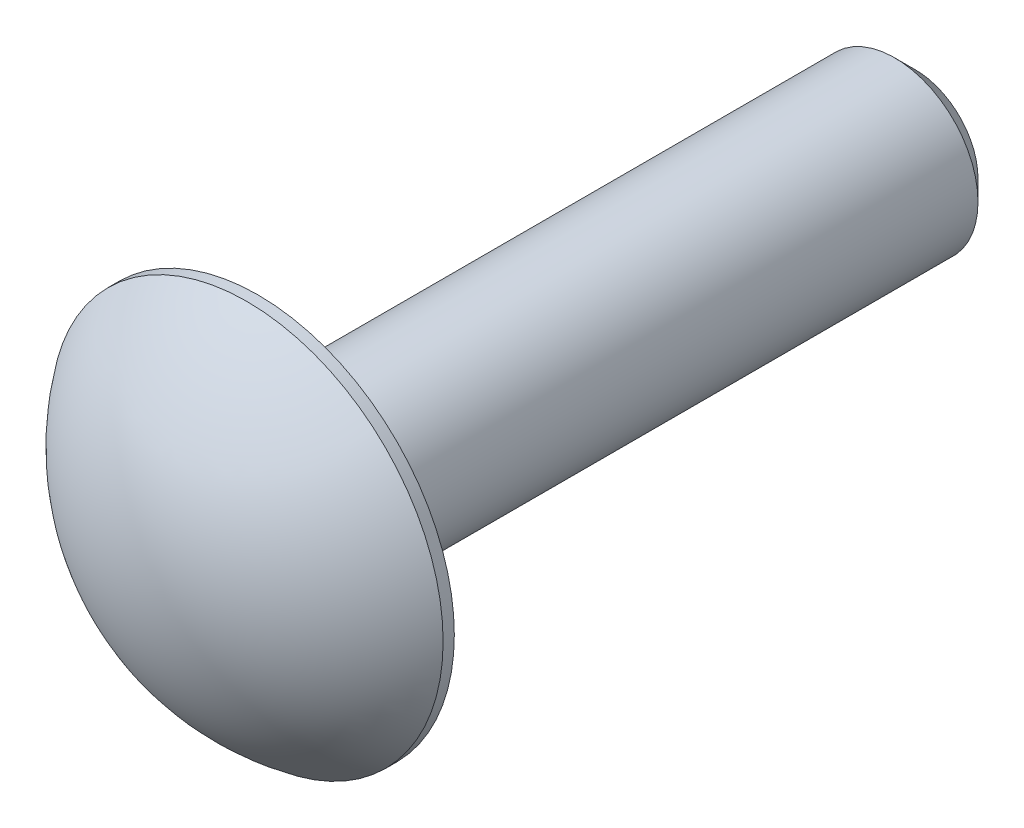
SolidWorks part; units mm, degrees
material "AISI 304"
ref_plane "Front" through (0, 0, 0) normal (0, 0, 1) x (1, 0, 0)
ref_plane "Top" through (0, 0, 0) normal (0, 1, 0) x (1, 0, 0)
ref_plane "Right" through (0, 0, 0) normal (1, 0, 0) x (0, 0, -1)
sketch "Sketch1" plane through (0, 0, 0) normal (0, 0, 1) x (1, 0, 0)
  circle A0 centre (0, 0) radius 5.6896
  dimension "Head Dia" = 11.3792
extrude "Extrude3" add sketch "Sketch1" along normal blind 3.2512
sketch "Sketch11" plane through (0, 0, 0) normal (1, 0, 0) x (0, 0, -1)
  line L0 (0, 0) -> (-3.5052, 0) construction
  line L4 (-3.2512, 5.6896) -> (-3.2512, -5.6896) construction
  line L5 (-3.5052, 6.8275) -> (0, 6.8275)
  line L7 (0, 6.8275) -> (0, 5.6896)
  line L8 (-0.3251, 5.6896) -> (0, 5.6896)
  line L9 (0, -5.6896) -> (0, 5.6896) construction
  line L11 (0, 5.6896) -> (-3.2512, 5.6896) construction
  line L13 (-3.2512, 0) -> (-3.5052, 0)
  line L14 (-3.5052, 0) -> (-3.5052, 6.8275)
  arc A0 (-0.3251, 5.6896) -> (-3.2512, 0) centre (3.7434, 0) ccw
  dimension "D3" = 0.254
  dimension "D1" = 0.3251
  dimension "D5" = 1.1379
revolve "Cut-Revolve3" cut sketch "Sketch11" angle 360 about L0
sketch "Sketch4" plane through (0, 0, 0) normal (1, 0, 0) x (0, 0, -1)
  line L0 (0, 0) -> (19.05, 0)
  line L3 (19.05, 0) -> (19.05, 2.413)
  line L4 (19.05, 2.413) -> (0, 2.413)
  line L6 (0, 2.413) -> (0, 0)
  line L9 (19.05, 2.413) -> (19.05, -2.413) construction
  dimension "length" = 19.05
  dimension "dia" = 4.826
revolve "Revolve1" add sketch "Sketch4" angle 360 about L0
sketch "Sketch13" plane through (0, 0, -19.05) normal (0, 0, -1) x (-1, 0, 0)
  circle A2 centre (0, 0) radius 2.413
curve "Helix/Spiral1" pitch 0.7937 height 22.3012 turns 28.096
chamfer "Chamfer2" distance 0.5953 angle 45 1 edges at (2.413, 0, -19.05)
sketch "Sketch14" plane through (0, 0, 0) normal (1, 0, 0) x (0, 0, -1)
  line L0 (19.05, 2.4378) -> (19.7445, 2.4378)
  line L1 (19.7445, 2.4378) -> (19.4469, 1.9008)
  line L2 (19.4469, 1.9008) -> (19.3477, 1.9008)
  line L3 (19.3477, 1.9008) -> (19.05, 2.4378)
  line L4 (19.1988, 2.1693) -> (19.5957, 2.1693) construction
  dimension "D1" = 0.0992
  dimension "D2" = 58
  dimension "D3" = 0.3969
  dimension "D4" = 0.0248
sweep "Cut-Sweep1" [suppressed] cut profiles "Sketch14" path "Helix/Spiral1"
ref_plane "Plane1" through (0, 0, 19.05) normal (0, 0, -1) x (-1, 0, 0)
sketch "Sketch29" [suppressed] plane through (0, 0, 28.575) normal (0, 0, -1) x (-1, 0, 0)
  circle A0 centre (0, 0) radius 1.7526 construction
  circle A1 centre (0, 0) radius 1.7526
  point P3 (0, -1.7526)
  point P4 (0, 1.7526)
extrude "Extrude11" [suppressed] add sketch "Sketch29" against normal up to surface (28.575 mm away) up to plane "Front"
ref_plane "Plane2" through (0, 0, 3.2512) normal (0, 0, 1) x (1, 0, 0)
sketch "Sketch26" plane through (0, 0, 0) normal (0, 0, 1) x (1, 0, 0)
  circle A1 centre (0, 0) radius 0.5461
  dimension "D1" = 1.0922
extrude "Extrude13" add sketch "Sketch26" along normal up to surface (3.2298 mm away)
sketch "Sketch31" plane through (0, 0, 3.2512) normal (0, 0, 1) x (1, 0, 0)
  line L0 (-5.6896, 0.6945) -> (5.6896, -0.6945) construction
  line L1 (-5.6896, 0.6945) -> (5.6896, 0.6945)
  line L2 (-5.6896, 0.6945) -> (-5.6896, -0.6945)
  line L3 (-5.6896, -0.6945) -> (5.6896, -0.6945)
  line L4 (5.6896, 0.6945) -> (5.6896, -0.6945)
  circle A0 centre (0, 0) radius 5.6896 construction
  dimension "D1" = 1.3891
extrude "Extrude15" [suppressed] cut sketch "Sketch31" against normal blind 1.6256
sketch "Sketch18" plane through (0, 0, 0) normal (1, 0, 0) x (0, 0, -1)
  line L1 (19.05, 2.413) -> (0, 2.413) construction
  point P0 (17.8594, -2.413)
  point P1 (18.2562, 2.413)
  point P2 (-3.2512, 0.6945)
  dimension "D1" = 0.7937
  dimension "D2" = 1.1906
equation "\"D3@Helix/Spiral1\" = \"length@Sketch4\" + \"Head Ht@Extrude3\""
equation "\"D1@Sketch14\" = \"D4@Helix/Spiral1\" * .125"
equation "\"D3@Sketch14\" = \"D4@Helix/Spiral1\" * .5"
equation "\"D1@Sketch11\" = \"Head Ht@Extrude3\" / 10"
equation "\"D5@Sketch11\" = \"Head Dia@Sketch1\" / 10"
equation "\"D4@Sketch14\" = \"D1@Sketch14\" * .25"
equation "\"D1@Chamfer2\" = \"D4@Helix/Spiral1\" * .75"
equation "\"D1@Sketch18\" = \"D4@Helix/Spiral1\""
equation "\"D2@Sketch18\" = \"D4@Helix/Spiral1\" * 1.5"
equation "\"D1@Extrude15\" = \"Head Ht@Extrude3\" * .5"
equation "\"D1@Sketch31\" = \"D4@Helix/Spiral1\" * 1.75"
